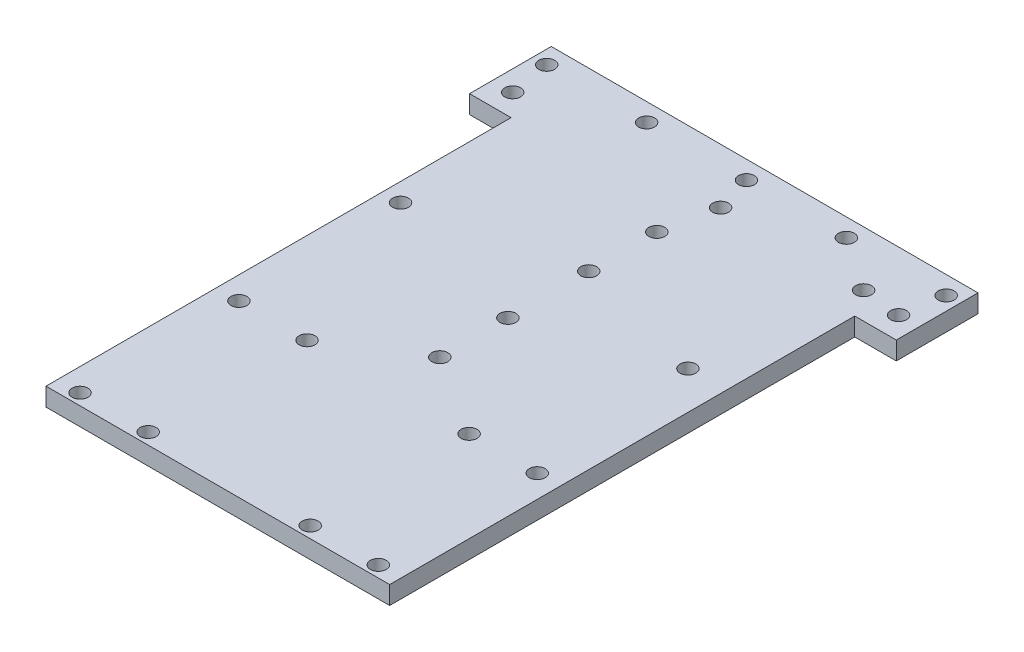
SolidWorks part; units mm, degrees
ref_plane "Front Plane" through (0, 0, 0) normal (0, 0, 1) x (1, 0, 0)
ref_plane "Top Plane" through (0, 0, 0) normal (0, 1, 0) x (1, 0, 0)
ref_plane "Right Plane" through (0, 0, 0) normal (1, 0, 0) x (0, 0, -1)
sketch "Sketch1" plane through (0, 0, 0) normal (0, 1, 0) x (1, 0, 0)
  line L1 (-37.85, 21.35) -> (37.85, 21.35)
  line L2 (-37.85, 21.35) -> (-37.85, -21.35)
  line L3 (-37.85, -21.35) -> (37.85, -21.35)
  line L4 (37.85, 21.35) -> (37.85, -21.35)
  line L5 (-37.85, 21.35) -> (37.85, -21.35) construction
  line L6 (-37.85, -21.35) -> (37.85, 21.35) construction
  circle A0 centre (2.4, 17.25) radius 1.75
  circle A1 centre (-33.8, -17.05) radius 1.75
  circle A2 centre (29.5, -17.05) radius 1.75
  circle A3 centre (33.9, 17.25) radius 1.75
  point P0 (0, 0)
  point P14 (0, 0)
  point P15 (0, 0)
  dimension "D9" = 3.5
  dimension "D1" = 75.7
  dimension "D2" = 42.7
  dimension "D3" = 4.1
  dimension "D4" = 4.3
  dimension "D5" = 4.05
  dimension "D6" = 8.35
  dimension "D7" = 3.95
  dimension "D8" = 40.25
extrude "Boss-Extrude1" add sketch "Sketch1" along normal blind 4
sketch "Sketch3" plane through (0, 4, 0) normal (0, 1, 0) x (1, 0, 0)
  line L0 (0, 0) -> (-31.55, 0) construction
  line L1 (-2.2, 0) -> (2.2, 0) construction
  line L2 (-31.55, 0) -> (-31.55, 14.5) construction
  line L3 (-31.55, 14.5) -> (27.25, 14.5) construction
  line L4 (27.25, 14.5) -> (27.25, -51.1) construction
  line L5 (27.25, -51.1) -> (-31.55, -51.1) construction
  line L6 (-31.55, -51.1) -> (-31.55, 0) construction
  line L7 (0, 14.5) -> (0, -51.1) construction
  line L8 (0, -2.2) -> (0, 2.2) construction
  line L9 (-31.55, -18.3) -> (27.25, -18.3) construction
  line L10 (-37.85, -21.35) -> (-37.85, -51.1)
  line L11 (37.85, -21.35) -> (37.85, -51.1)
  line L12 (37.85, -51.1) -> (-37.85, -51.1)
  line L13 (-37.85, -21.35) -> (37.85, -21.35)
  circle A0 centre (0, 5.6) radius 1.75
  circle A1 centre (0, -9.4) radius 1.75
  circle A2 centre (0, -27.2) radius 1.75
  circle A3 centre (0, -42.2) radius 1.75
  line M18 (-37.85, -21.35) -> (37.85, -21.35)
  dimension "D10" = 3.5
  dimension "D1" = 58.8
  dimension "D2" = 31.55
  dimension "D3" = 65.6
  dimension "D4" = 14.5
  dimension "D5" = 32.8
  dimension "D6" = 15
  dimension "D7" = 15
  dimension "D8" = 8.9
  dimension "D9" = 8.9
extrude "Boss-Extrude2" add sketch "Sketch3" against normal blind 4 contours L12 L11 L10 A3 A2 M18 region at (0, 4, 36.2381)
extrude "Cut-Extrude1" cut sketch "Sketch3<3>" against normal blind 4 contours A0 | A1
sketch "Sketch3<3>" plane through (0, 4, 0) normal (0, 1, 0) x (1, 0, 0) same geometry as "Sketch3"
sketch "Sketch4" plane through (0, 0, 0) normal (0, 1, 0) x (1, 0, 0)
  line L0 (-37.85, -51.1) -> (-37.85, -91.1) construction
  line L1 (-37.85, -91.1) -> (37.85, -91.1) construction
  line L2 (37.85, 21.35) -> (44, 21.35) construction
  line L3 (44, 21.35) -> (44, 29.35) construction
  line L4 (-37.85, 21.35) -> (-44, 21.35) construction
  line L6 (37.85, -51.1) -> (37.85, -91.1) construction
  line L7 (-44, 21.35) -> (-44, 29.35) construction
  line L8 (-44, 29.35) -> (44, 29.35) construction
  line L10 (-37.85, -51.1) -> (-37.85, -91.1)
  line L11 (-37.85, -91.1) -> (37.85, -91.1)
  line L12 (37.85, -91.1) -> (37.85, -51.1)
  line L13 (37.85, -51.1) -> (-37.85, -51.1)
  line L14 (-37.85, 21.35) -> (-44, 21.35)
  line L15 (-44, 21.35) -> (-44, 29.35)
  line L16 (-44, 29.35) -> (44, 29.35)
  line L17 (44, 29.35) -> (44, 21.35)
  line L18 (44, 21.35) -> (37.85, 21.35)
  line L19 (37.85, 21.35) -> (-37.85, 21.35)
  line L20 (0, -2.2) -> (0, 2.2) construction
  circle A0 centre (-32.85, -53.6) radius 1.75
  circle A1 centre (-17.85, -53.6) radius 1.75
  circle A2 centre (-17.85, -88.6) radius 1.75
  circle A3 centre (-32.85, -88.6) radius 1.75
  circle A4 centre (32.85, -88.6) radius 1.75
  circle A5 centre (17.85, -88.6) radius 1.75
  circle A6 centre (17.85, -53.6) radius 1.75
  circle A7 centre (32.85, -53.6) radius 1.75
  point P24 (0, 0)
  point P25 (0, 0)
  point P26 (0, 0)
  point P27 (0, 0)
  point P28 (0, 0)
  dimension "D5" = 3.5
  dimension "D1" = 88
  dimension "D2" = 8
  dimension "D3" = 40
  dimension "D4" = 6.15
  dimension "D6" = 15
  dimension "D7" = 5
  dimension "D8" = 2.5
  dimension "D9" = 2.5
extrude "Boss-Extrude3" add sketch "Sketch4" along normal blind 4
sketch "Sketch6" plane through (0, 4, 0) normal (0, 1, 0) x (1, 0, 0)
  line L0 (-44, 25.35) -> (44, 25.35) construction
  line L1 (-44, 29.35) -> (-44, 21.35) construction
  line L2 (44, 21.35) -> (44, 29.35) construction
  line L3 (-44, 29.35) -> (-47, 29.35)
  line L4 (-47, 29.35) -> (-47, 21.35)
  line L5 (-47, 21.35) -> (-44, 21.35)
  line L6 (44, 29.35) -> (47, 29.35)
  line L7 (47, 29.35) -> (47, 21.35)
  line L8 (47, 21.35) -> (44, 21.35)
  line L9 (44, 21.35) -> (44, 23.6)
  line L10 (44, 29.35) -> (44, 27.1)
  line L11 (-44, 21.35) -> (-44, 23.6)
  line L12 (-44, 29.35) -> (-44, 27.1)
  circle A0 centre (0, 25.35) radius 1.75
  circle A1 centre (22, 25.35) radius 1.75
  circle A2 centre (44, 25.35) radius 1.75
  circle A3 centre (-22, 25.35) radius 1.75
  circle A4 centre (-44, 25.35) radius 1.75
  line M16 (44, 21.35) -> (44, 29.35)
  line M18 (-44, 29.35) -> (-44, 21.35)
  dimension "D5" = 3.5
  dimension "D1" = 22
  dimension "D2" = 22
  dimension "D3" = 22
  dimension "D4" = 22
  dimension "D6" = 3
  dimension "D7" = 3
extrude "Boss-Extrude4" add sketch "Sketch6" against normal blind 4 contours A4 L3 L4 L5 M18 | A2 L8 L7 L6 M16 region at (-44.0854, 4, -28.225) region at (45.5, 4, -29.2646)
extrude "Cut-Extrude2" cut sketch "Sketch6<3>" against normal through all contours A4 | A3 | A1 | A2 | A0
sketch "Sketch6<3>" plane through (0, 4, 0) normal (0, 1, 0) x (1, 0, 0) same geometry as "Sketch6"
sketch "Sketch7" plane through (0, 0, 0) normal (0, 1, 0) x (1, 0, 0)
  line L0 (-47, 21.35) -> (-47, 11.35)
  line L1 (-47, 11.35) -> (-37.85, 11.35)
  line L2 (-37.85, 21.35) -> (-37.85, -91.1) construction
  line L3 (-37.85, 11.35) -> (-37.85, 21.35)
  line L4 (-37.85, 21.35) -> (-47, 21.35)
  line L5 (47, 21.35) -> (47, 11.35)
  line L6 (47, 11.35) -> (37.85, 11.35)
  line L7 (37.85, -91.1) -> (37.85, 21.35) construction
  line L8 (37.85, 11.35) -> (37.85, 21.35)
  line L9 (37.85, 21.35) -> (47, 21.35)
  circle A0 centre (-42.5, 16.35) radius 1.75
  circle A1 centre (42.5, 16.35) radius 1.75
  point P20 (0, 0)
  dimension "D6" = 3.5
  dimension "D1" = 10
  dimension "D2" = 10
  dimension "D3" = 4.5
  dimension "D4" = 4.5
  dimension "D5" = 5
extrude "Boss-Extrude5" add sketch "Sketch7" along normal blind 4
